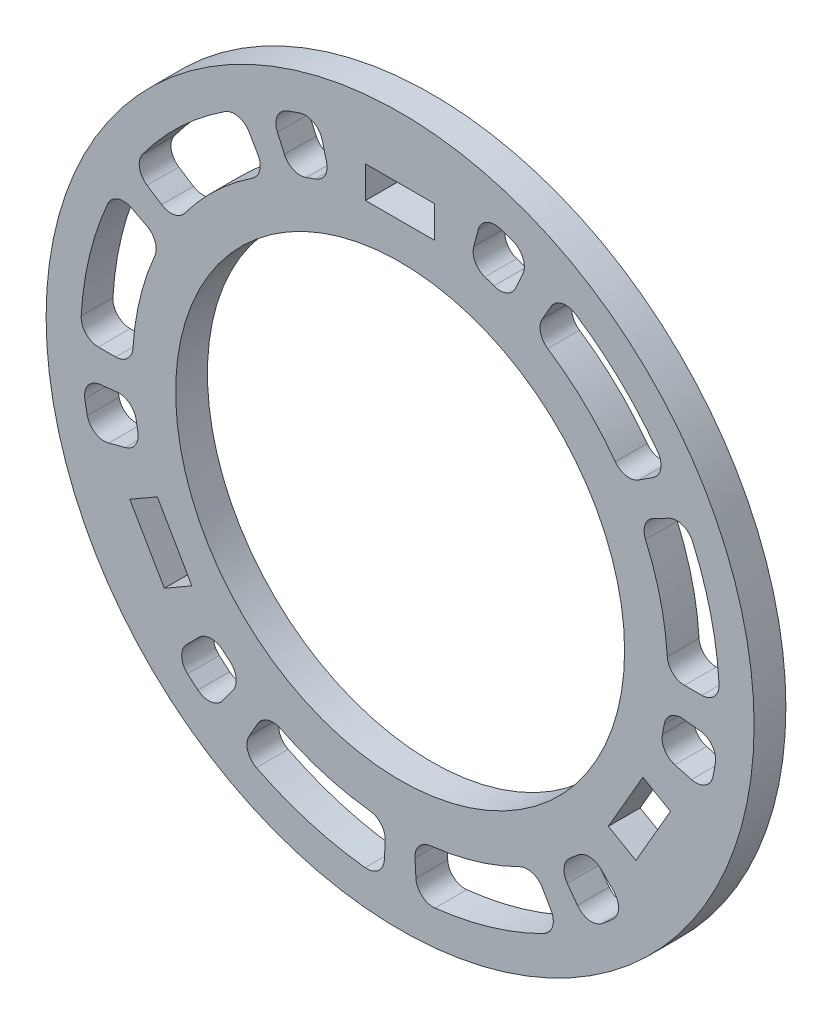
SolidWorks part; units mm, degrees
ref_plane "Front Plane" through (0, 0, 0) normal (0, 0, 1) x (1, 0, 0)
ref_plane "Top Plane" through (0, 0, 0) normal (0, 1, 0) x (1, 0, 0)
ref_plane "Right Plane" through (0, 0, 0) normal (1, 0, 0) x (0, 0, -1)
sketch "Sketch1" plane through (0, 0, 0) normal (0, 0, 1) x (1, 0, 0)
  line L0 (0, 0) -> (0, 50.8) construction
  line L2 (6.35, 53.721) -> (-6.35, 53.721)
  line L3 (6.35, 53.721) -> (6.35, 47.879)
  line L4 (6.35, 47.879) -> (-6.35, 47.879)
  line L5 (-6.35, 53.721) -> (-6.35, 47.879)
  line L6 (6.35, 53.721) -> (-6.35, 47.879) construction
  line L7 (6.35, 47.879) -> (-6.35, 53.721) construction
  line L11 (49.6988, -21.3612) -> (44.6394, -18.4402)
  line L12 (43.3488, -32.3598) -> (49.6988, -21.3612)
  line L13 (43.3488, -32.3598) -> (38.2894, -29.4388)
  line L14 (38.2894, -29.4388) -> (44.6394, -18.4402)
  line L19 (-43.3488, -32.3598) -> (-38.2894, -29.4388)
  line L20 (-49.6988, -21.3612) -> (-43.3488, -32.3598)
  line L21 (-49.6988, -21.3612) -> (-44.6394, -18.4402)
  line L22 (-44.6394, -18.4402) -> (-38.2894, -29.4388)
  line L27 (0, 0) -> (32.5438, 56.3674) construction
  line L28 (-43.3488, 32.3598) -> (-49.6988, 21.3612) [skipped]
  line L29 (-38.2894, 29.4388) -> (-44.6394, 18.4402) [skipped]
  line L30 (-49.6988, 21.3612) -> (-46.824, 19.7015) [skipped]
  line L31 (-40.474, 30.7) -> (-38.2894, 29.4388) [skipped]
  line L32 (6.35, -53.721) -> (6.35, -47.879) [skipped]
  line L33 (-6.35, -53.721) -> (-6.35, -47.879) [skipped]
  line L34 (-6.35, -47.879) -> (6.35, -47.879) [skipped]
  line L35 (-6.35, -53.721) -> (6.35, -53.721) [skipped]
  line L36 (43.3488, 32.3598) -> (38.2894, 29.4388) [skipped]
  line L37 (49.6988, 21.3612) -> (43.3488, 32.3598) [skipped]
  line L38 (49.6988, 21.3612) -> (44.6394, 18.4402) [skipped]
  line L39 (44.6394, 18.4402) -> (38.2894, 29.4388) [skipped]
  circle A0 centre (0, 0) radius 41.275
  circle A1 centre (0, 0) radius 65.0875
  circle A2 centre (0, 0) radius 50.8 construction
  point P32 (0, 0)
  dimension "D1" = 82.55
  dimension "D2" = 130.175
  dimension "D3" = 50.8
  dimension "D4" = 12.7
  dimension "D5" = 5.842
  dimension "D7" = 30
  dimension "D6" = 6
extrude "Boss-Extrude1" add sketch "Sketch1" along normal blind 5.842
sketch "Sketch3" plane through (0, 0, 5.842) normal (0, 0, 1) x (1, 0, 0)
  line L0 (0, 0) -> (0, 65.0875) construction
  line L1 (0, 0) -> (-56.3674, 32.5437) construction
  line L2 (-24.6063, 42.6193) -> (-29.3688, 50.8682)
  line L3 (-49.2125, 0) -> (-58.7375, 0)
  line L4 (-41.2731, 26.803) -> (-49.2614, 31.9907)
  line L5 (-43.8487, 22.342) -> (-52.3355, 26.6663)
  line L6 (43.8487, 22.342) -> (52.3355, 26.6663)
  line L7 (41.2731, 26.803) -> (49.2614, 31.9907)
  line L8 (24.6063, 42.6193) -> (29.3688, 50.8682)
  line L9 (49.2125, 0) -> (58.7375, 0)
  line L10 (-2.5756, -49.1451) -> (-3.0741, -58.657)
  line L11 (2.5756, -49.1451) -> (3.0741, -58.657)
  line L12 (24.6062, -42.6193) -> (29.3687, -50.8682)
  line L13 (-24.6063, -42.6193) -> (-29.3688, -50.8682)
  line L14 (-20.0165, 44.9579) -> (-23.8907, 53.6594)
  line L15 (-15.2024, 56.7361) -> (-12.7371, 47.5356)
  line L16 (-56.7361, -15.2024) -> (-47.5356, -12.7371)
  line L17 (-48.9429, -5.1441) -> (-58.4157, -6.1397)
  line L18 (48.9429, -5.1441) -> (58.4157, -6.1397)
  line L19 (56.7361, -15.2024) -> (47.5356, -12.7371)
  line L20 (15.2024, 56.7361) -> (12.7371, 47.5356)
  line L21 (20.0165, 44.9579) -> (23.8907, 53.6594)
  line L22 (-28.9264, -39.8137) -> (-34.525, -47.5196)
  line L23 (-41.5337, -41.5337) -> (-34.7985, -34.7985)
  line L24 (41.5337, -41.5337) -> (34.7985, -34.7985)
  line L25 (28.9264, -39.8137) -> (34.525, -47.5196)
  circle A0 centre (0, 0) radius 65.0875 construction
  arc A1 (-29.3688, 50.8682) -> (-49.2614, 31.9907) centre (0, 0) ccw
  arc A2 (-24.6063, 42.6193) -> (-41.2731, 26.803) centre (0, 0) ccw
  arc A3 (-43.8487, 22.342) -> (-49.2125, 0) centre (0, 0) ccw
  circle A4 centre (0, 0) radius 49.2125 construction
  circle A5 centre (0, 0) radius 58.7375 construction
  arc A6 (-52.3355, 26.6663) -> (-58.7375, 0) centre (0, 0) ccw
  arc A7 (58.7375, 0) -> (52.3355, 26.6663) centre (0, 0) ccw
  arc A8 (49.2614, 31.9907) -> (29.3688, 50.8682) centre (0, 0) ccw
  arc A9 (41.2731, 26.803) -> (24.6063, 42.6193) centre (0, 0) ccw
  arc A10 (49.2125, 0) -> (43.8487, 22.342) centre (0, 0) ccw
  arc A11 (-29.3688, -50.8682) -> (-3.0741, -58.657) centre (0, 0) ccw
  arc A12 (3.0741, -58.657) -> (29.3687, -50.8682) centre (0, 0) ccw
  arc A13 (2.5756, -49.1451) -> (24.6062, -42.6193) centre (0, 0) ccw
  arc A14 (-24.6063, -42.6193) -> (-2.5756, -49.1451) centre (0, 0) ccw
  arc A15 (-24.6063, 42.6193) -> (-41.2731, 26.803) centre (0, 0) ccw
  arc A16 (-29.3688, 50.8682) -> (-49.2614, 31.9907) centre (0, 0) ccw
  arc A17 (-43.8487, 22.342) -> (-49.2125, 0) centre (0, 0) ccw
  arc A18 (-52.3355, 26.6663) -> (-58.7375, 0) centre (0, 0) ccw
  arc A19 (-24.6063, -42.6193) -> (-2.5756, -49.1451) centre (0, 0) ccw
  arc A20 (-29.3688, -50.8682) -> (-3.0741, -58.657) centre (0, 0) ccw
  arc A21 (2.5756, -49.1451) -> (24.6062, -42.6193) centre (0, 0) ccw
  arc A22 (3.0741, -58.657) -> (29.3687, -50.8682) centre (0, 0) ccw
  arc A23 (58.7375, 0) -> (52.3355, 26.6663) centre (0, 0) ccw
  arc A24 (49.2125, 0) -> (43.8487, 22.342) centre (0, 0) ccw
  arc A25 (41.2731, 26.803) -> (24.6063, 42.6193) centre (0, 0) ccw
  arc A26 (49.2614, 31.9907) -> (29.3688, 50.8682) centre (0, 0) ccw
  arc A27 (-12.7371, 47.5356) -> (-20.0165, 44.9579) centre (0, 0) ccw
  arc A28 (-15.2024, 56.7361) -> (-23.8907, 53.6594) centre (0, 0) ccw
  arc A29 (-56.7361, -15.2024) -> (-58.4157, -6.1397) centre (0, 0) cw
  arc A30 (-47.5356, -12.7371) -> (-48.9429, -5.1441) centre (0, 0) cw
  arc A31 (56.7361, -15.2024) -> (58.4157, -6.1397) centre (0, 0) ccw
  arc A32 (47.5356, -12.7371) -> (48.9429, -5.1441) centre (0, 0) ccw
  arc A33 (15.2024, 56.7361) -> (23.8907, 53.6594) centre (0, 0) cw
  arc A34 (12.7371, 47.5356) -> (20.0165, 44.9579) centre (0, 0) cw
  arc A35 (-41.5337, -41.5337) -> (-34.525, -47.5196) centre (0, 0) ccw
  arc A36 (-34.7985, -34.7985) -> (-28.9264, -39.8137) centre (0, 0) ccw
  arc A37 (41.5337, -41.5337) -> (34.525, -47.5196) centre (0, 0) cw
  arc A38 (34.7985, -34.7985) -> (28.9264, -39.8137) centre (0, 0) cw
  point P8 (56.171, 17.1732)
  point P13 (49.2125, 0)
  point P38 (0, 0)
  point P63 (0, 0)
  dimension "D2" = 117.475
  dimension "D1" = 60
  dimension "D4" = 30
  dimension "D5" = 3
  dimension "D7" = 36
  dimension "D8" = 45
  dimension "D3" = 9.525
  dimension "D6" = 3
  dimension "D9" = 3
extrude "Cut-Extrude2" cut sketch "Sketch3" against normal through all contours A2 L2 A1 L4 | L5 A6 L3 A3 | L16 A30 L17 A29 | L15 A28 L14 A27 | L20 A34 L21 A33 | A9 L7 A8 L8 | A10 L9 A7 L6 | A32 L19 A31 L18 | L24 A38 L25 A37 | A13 L11 A12 L12 | A14 L13 A11 L10 | A36 L23 A35 L22 region at (-36.9066, 38.8915, 5.842) region at (-52.1343, 12.5163, 5.842) region at (52.1343, 12.5163, 5.842) region at (36.9066, 38.8915, 5.842) region at (-15.2277, -51.4078, 5.842) region at (15.2277, -51.4078, 5.842) region at (-18.0454, 50.9587, 5.842) region at (-53.1542, -9.8516, 5.842) region at (53.1542, -9.8516, 5.842) region at (18.0454, 50.9587, 5.842) region at (-35.1088, -41.1071, 5.842) region at (35.1088, -41.1071, 5.842)
fillet "Fillet1" radius 3.175 48 edges at (-52.3355, 26.6663, 2.921) (-58.4157, -6.1397, 2.921) (-43.8487, 22.342, 2.921) (-48.9429, -5.1441, 2.921) (-58.7375, 0, 2.921) (-56.7361, -15.2024, 2.921) (-47.5356, -12.7371, 2.921) (-49.2125, 0, 2.921) (-41.2731, 26.803, 2.921) (-49.2614, 31.9907, 2.921) (-20.0165, 44.9579, 2.921) (-12.7371, 47.5356, 2.921) (-15.2024, 56.7361, 2.921) (-23.8907, 53.6594, 2.921) (-29.3688, 50.8682, 2.921) (-24.6063, 42.6193, 2.921) (41.5337, -41.5337, 2.921) (34.525, -47.5196, 2.921) (34.7985, -34.7985, 2.921) (28.9264, -39.8137, 2.921) (3.0741, -58.657, 2.921) (2.5756, -49.1451, 2.921) (24.6062, -42.6193, 2.921) (29.3687, -50.8682, 2.921) (-3.0741, -58.657, 2.921) (-2.5756, -49.1451, 2.921) (-29.3688, -50.8682, 2.921) (-24.6063, -42.6193, 2.921) (-28.9264, -39.8137, 2.921) (-41.5337, -41.5337, 2.921) (-34.7985, -34.7985, 2.921) (-34.525, -47.5196, 2.921) (48.9429, -5.1441, 2.921) (58.4157, -6.1397, 2.921) (56.7361, -15.2024, 2.921) (47.5356, -12.7371, 2.921) (58.7375, 0, 2.921) (49.2125, 0, 2.921) (52.3355, 26.6663, 2.921) (43.8487, 22.342, 2.921) (49.2614, 31.9907, 2.921) (41.2731, 26.803, 2.921) (29.3688, 50.8682, 2.921) (23.8907, 53.6594, 2.921) (15.2024, 56.7361, 2.921) (24.6063, 42.6193, 2.921) (12.7371, 47.5356, 2.921) (20.0165, 44.9579, 2.921)
